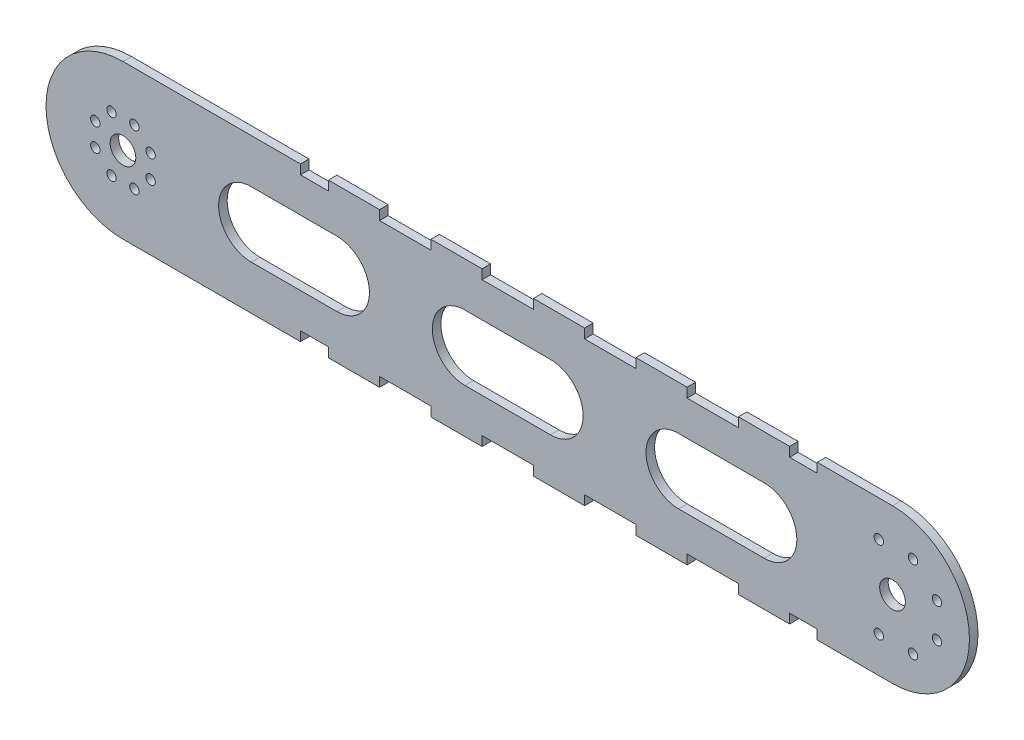
SolidWorks part; units mm, degrees
ref_plane "Front Plane" through (0, 0, 0) normal (0, 0, 1) x (1, 0, 0)
ref_plane "Top Plane" through (0, 0, 0) normal (0, 1, 0) x (1, 0, 0)
ref_plane "Right Plane" through (0, 0, 0) normal (1, 0, 0) x (0, 0, -1)
sketch "Sketch3" plane through (0, 0, 0) normal (0, 0, 1) x (1, 0, 0)
  line L0 (-20.9627, 0) -> (429.0373, 0) construction
  line L1 (-20.9627, 45) -> (429.0373, 45)
  line L2 (-20.9627, -45) -> (429.0373, -45)
  line L3 (179.0373, 0) -> (229.0373, 0) construction
  line L4 (179.0373, 19.0946) -> (229.0373, 19.0946)
  line L5 (179.0373, -19.0946) -> (229.0373, -19.0946)
  line L9 (-20.9627, 0) -> (-4.7949, 6.697)
  line L10 (-20.9627, 0) -> (-4.7949, 6.697) construction
  line L11 (-20.9627, 0) -> (-4.7949, -6.697) construction
  line L36 (-101.4371, 0) -> (436.7316, 0) construction
  line L64 (304.0053, 0) -> (354.0053, 0) construction
  line L65 (304.0053, 19.0946) -> (354.0053, 19.0946)
  line L66 (304.0053, -19.0946) -> (354.0053, -19.0946)
  line L67 (54.0693, 0) -> (104.0693, 0) construction
  line L68 (54.0693, 19.0946) -> (104.0693, 19.0946)
  line L69 (54.0693, -19.0946) -> (104.0693, -19.0946)
  line L70 (248.9813, 45) -> (248.9813, 39.46)
  line L71 (189.0373, 45) -> (219.0373, 45)
  line L72 (189.0373, 45) -> (189.0373, 39.46)
  line L73 (189.0373, 39.46) -> (219.0373, 39.46)
  line L74 (219.0373, 45) -> (219.0373, 39.46)
  line L75 (248.9813, 45) -> (278.9813, 45)
  line L76 (278.9813, 45) -> (278.9813, 39.46)
  line L77 (248.9813, 39.46) -> (278.9813, 39.46)
  line L78 (308.9253, 45) -> (308.9253, 39.46)
  line L79 (308.9253, 45) -> (338.9253, 45)
  line L80 (338.9253, 45) -> (338.9253, 39.46)
  line L81 (308.9253, 39.46) -> (338.9253, 39.46)
  line L82 (129.0933, 45) -> (129.0933, 39.46)
  line L83 (129.0933, 45) -> (159.0933, 45)
  line L84 (159.0933, 45) -> (159.0933, 39.46)
  line L85 (129.0933, 39.46) -> (159.0933, 39.46)
  line L86 (69.1493, 45) -> (69.1493, 39.46)
  line L87 (69.1493, 45) -> (99.1493, 45)
  line L88 (99.1493, 45) -> (99.1493, 39.46)
  line L89 (69.1493, 39.46) -> (99.1493, 39.46)
  line L94 (82.808, 39.46) -> (82.808, 45)
  line L95 (368.8693, 45) -> (368.8693, 39.46)
  line L96 (368.8693, 39.46) -> (398.8693, 39.46)
  line L97 (398.8693, 45) -> (398.8693, 39.46)
  line L98 (368.8693, 45) -> (398.8693, 45)
  line L99 (385.0007, 45) -> (385.0007, 39.46)
  arc A0 (-20.9627, 45) -> (-20.9627, -45) centre (-20.9627, 0) ccw
  arc A1 (429.0373, -45) -> (429.0373, 45) centre (429.0373, 0) ccw
  circle A2 centre (-20.9627, 0) radius 7.5
  circle A3 centre (429.0373, 0) radius 7.5
  arc A4 (179.0373, 19.0946) -> (179.0373, -19.0946) centre (179.0373, 0) ccw
  arc A5 (229.0373, -19.0946) -> (229.0373, 19.0946) centre (229.0373, 0) ccw
  circle A8 centre (-4.7949, 6.697) radius 2.75
  circle A9 centre (-4.7949, -6.697) radius 2.75
  circle A10 centre (-14.2658, -16.1679) radius 2.75
  circle A11 centre (-27.6597, -16.1679) radius 2.75
  circle A12 centre (-37.1306, -6.697) radius 2.75
  circle A13 centre (-37.1306, 6.697) radius 2.75
  circle A14 centre (-27.6597, 16.1679) radius 2.75
  circle A15 centre (-14.2658, 16.1679) radius 2.75
  circle A16 centre (455.0373, 10) radius 2.75
  circle A17 centre (441.0373, 24) radius 2.75
  circle A18 centre (421.0373, 24) radius 2.75
  circle A19 centre (455.0373, -10) radius 2.75
  circle A20 centre (441.0373, -24) radius 2.75
  circle A21 centre (421.0373, -24) radius 2.75
  arc A22 (304.0053, 19.0946) -> (304.0053, -19.0946) centre (304.0053, 0) ccw
  arc A23 (354.0053, -19.0946) -> (354.0053, 19.0946) centre (354.0053, 0) ccw
  arc A24 (54.0693, 19.0946) -> (54.0693, -19.0946) centre (54.0693, 0) ccw
  arc A25 (104.0693, -19.0946) -> (104.0693, 19.0946) centre (104.0693, 0) ccw
  point P3 (204.0373, 0)
  point P14 (204.0373, 0)
  point P23 (204.0373, 39.46)
  point P59 (329.0053, 0)
  point P66 (79.0693, 0)
  dimension "D2" = 45
  dimension "D3" = 15
  dimension "D4" = 15
  dimension "D7" = 5.5
  dimension "D21" = 5.5
  dimension "D22" = 5.5
  dimension "D23" = 5.5
  dimension "D1" = 450
  dimension "D5" = 17.5
  dimension "D6" = 22.5
  dimension "D9" = 45
  dimension "D10" = 5.54
  dimension "D11" = 30
  dimension "D12" = 3
  dimension "D15" = 24
  dimension "D16" = 24
  dimension "D17" = 8
  dimension "D18" = 20
  dimension "D19" = 26
  dimension "D20" = 10
  dimension "D24" = 50
  dimension "D25" = 0
  dimension "D26" = 2
  dimension "D14" = 2
  dimension "D13" = 3
  dimension "D28" = 2
  dimension "D8" = 8
extrude "Boss-Extrude1" add sketch "Sketch3" along normal blind 5 contours L2 A1 L1 L97 L96 L95 L80 L81 L78 L76 L77 L70 L74 L73 L72 L84 L85 L82 L88 L89 L86 A0 A25 L69 A24 L68 A23 L66 A22 L65 A20 A3 A5 L5 A4 L4 A8 | L89 L94 L1 L86 | L94 L89 L88 L87 | L82 L85 L84 L1 | L74 L1 L72 L73 | L70 L77 L76 L1 | L78 L81 L80 L1 | L99 L1 L95 L96 | L98 L99 L96 L97 region at (24.0933, 39.5255, 0) region at (75.9786, 42.23, 0) region at (90.9786, 42.23, 0) region at (144.0933, 42.23, 0) region at (391.935, 42.23, 0) region at (376.935, 42.23, 0) region at (204.0373, 42.23, 0) region at (323.9253, 42.23, 0) region at (263.9813, 42.23, 0)
extrude "Cut-Extrude1" cut sketch "Sketch3<3>" along normal through all contours L94 L89 L88 L87 | L82 L85 L84 L1 | L74 L1 L72 L73 | L70 L77 L76 L1 | L78 L81 L80 L1 | L99 L1 L95 L96 region at (90.9786, 42.23, 0) region at (144.0933, 42.23, 0) region at (376.935, 42.23, 0) region at (204.0373, 42.23, 0) region at (323.9253, 42.23, 0) region at (263.9813, 42.23, 0)
sketch "Sketch3<3>" plane through (0, 0, 0) normal (0, 0, 1) x (1, 0, 0) same geometry as "Sketch3"
mirror "Mirror1" about plane through (0, 0, 0) normal (0, 1, 0) of "Cut-Extrude1"
